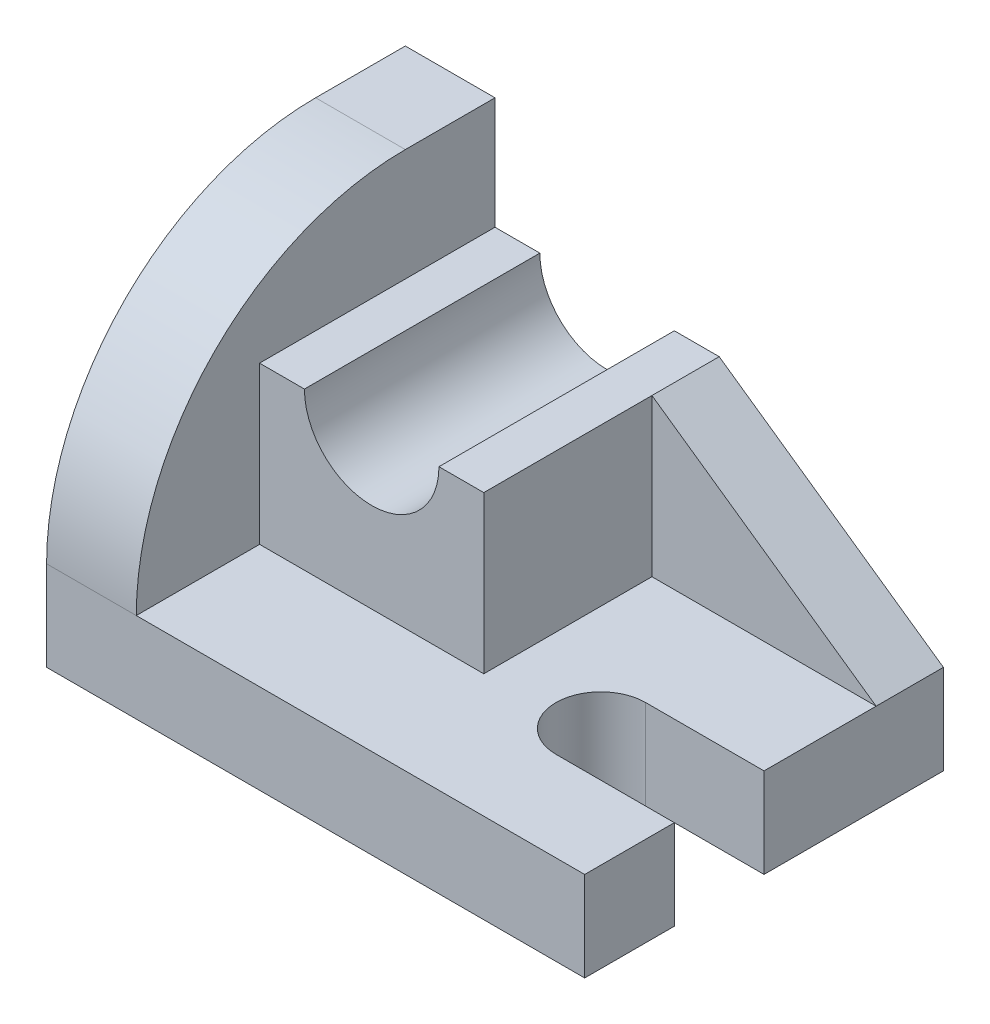
SolidWorks part; units mm, degrees
ref_plane "Front Plane" through (0, 0, 0) normal (0, 0, 1) x (1, 0, 0)
ref_plane "Top Plane" through (0, 0, 0) normal (0, 1, 0) x (1, 0, 0)
ref_plane "Right Plane" through (0, 0, 0) normal (1, 0, 0) x (0, 0, -1)
sketch "Sketch1" plane through (0, 0, 0) normal (0, 1, 0) x (1, 0, 0)
  line L0 (186.6013, 121.92) -> (-57.2387, 121.92)
  line L1 (-57.2387, 121.92) -> (-57.2387, -40.64)
  line L2 (-57.2387, -40.64) -> (186.6013, -40.64)
  line L3 (186.6013, -40.64) -> (186.6013, 0)
  line L4 (186.6013, 0) -> (132.9485, 0)
  line L5 (186.6013, 121.92) -> (186.6013, 40.64)
  line L6 (186.6013, 40.64) -> (132.9485, 40.64)
  arc A0 (132.9485, 0) -> (132.9485, 40.64) centre (132.9485, 20.32) cw
  point P10 (159.7749, 0)
  dimension "D1" = 162.56
  dimension "D4" = 20.32
  dimension "D2" = 243.84
  dimension "D3" = 40.64
extrude "Boss-Extrude1" add sketch "Sketch1" along normal blind 40.64
sketch "Sketch2" plane through (0, 40.64, 0) normal (0, 1, 0) x (1, 0, 0)
  line L0 (-16.5987, 121.92) -> (-16.5987, -40.64)
  line L1 (186.6013, 121.92) -> (-57.2387, 121.92) construction
  line L2 (-57.2387, -40.64) -> (186.6013, -40.64) construction
  line L3 (-16.5987, -40.64) -> (-57.2387, -40.64)
  line L4 (-57.2387, -40.64) -> (-57.2387, 121.92)
  line L5 (-57.2387, 121.92) -> (-16.5987, 121.92)
  line L6 (-16.5987, 15.24) -> (85.0013, 15.24)
  line L7 (85.0013, 15.24) -> (85.0013, 91.44)
  line L8 (85.0013, 91.44) -> (186.6013, 91.44)
  line L9 (186.6013, 40.64) -> (186.6013, 121.92) construction
  line L10 (186.6013, 91.44) -> (186.6013, 121.92)
  line L11 (186.6013, 121.92) -> (-16.5987, 121.92)
  line L12 (-16.5987, 15.24) -> (-16.5987, 121.92)
  line M8 (186.6013, 121.92) -> (-57.2387, 121.92)
  line M9 (-57.2387, 121.92) -> (-57.2387, -40.64)
  line M10 (-57.2387, -40.64) -> (186.6013, -40.64)
  dimension "D1" = 40.64
  dimension "D2" = 30.48
  dimension "D3" = 55.88
  dimension "D4" = 101.6
extrude "Boss-Extrude2" add sketch "Sketch2" along normal blind 121.92 contours L0 M8 M9 M10 region at (-36.9187, 40.64, -40.64)
extrude "Boss-Extrude3" add sketch "Sketch2<4>" along normal blind 71.12 contours L12 L6 L7 L8 L10 L11
sketch "Sketch2<4>" plane through (0, 40.64, 0) normal (0, 1, 0) x (1, 0, 0) same geometry as "Sketch2"
chamfer "Chamfer1" distance 71.12 distance2 101.6 1 edges at (186.6013, 111.76, -106.68) first distance on face at (186.6013, 50.8, -84.6667)
fillet "Fillet1" radius 121.92 1 edges at (-36.9187, 162.56, 40.64)
sketch "Sketch3" plane through (0, 0, -15.24) normal (0, 0, 1) x (1, 0, 0)
  line L0 (-16.5987, 111.76) -> (85.0013, 111.76) construction
  line L1 (85.0013, 111.76) -> (64.6813, 111.76)
  line L2 (3.7213, 111.76) -> (64.6813, 111.76)
  arc A0 (64.6813, 111.76) -> (3.7213, 111.76) centre (34.2013, 111.76) cw
  line M4 (85.0013, 111.76) -> (-16.5987, 111.76)
  dimension "D1" = 30.48
  dimension "D2" = 20.32
extrude "Cut-Extrude1" cut sketch "Sketch3" against normal blind 106.68 contours A0 M4 region at (34.2013, 98.8239, -15.24)
